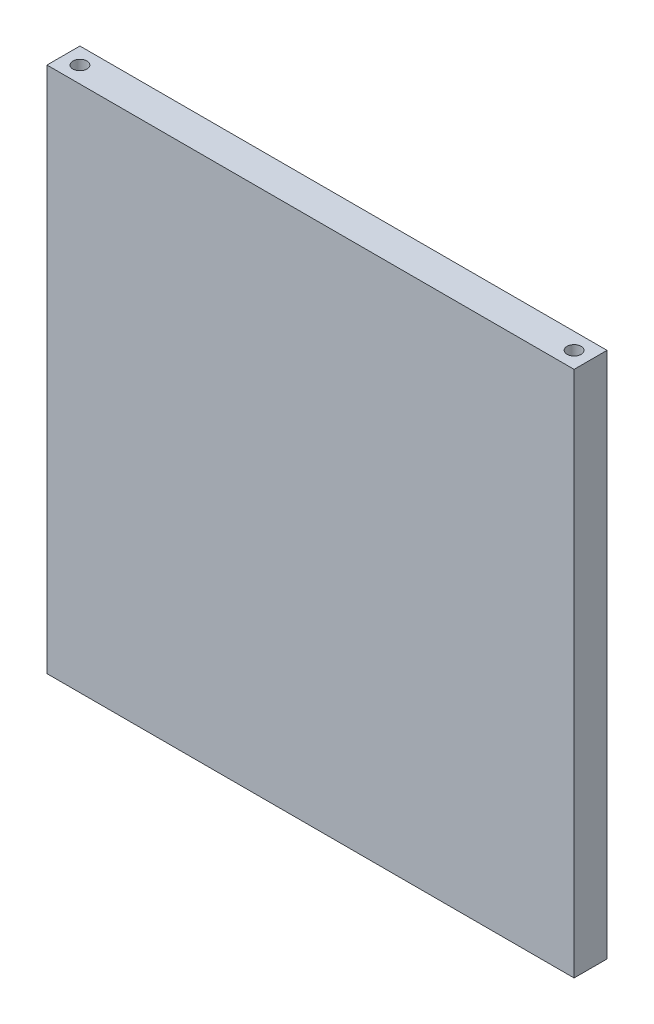
SolidWorks part; units mm, degrees
material "Acrylic (Medium-high impact)"
ref_plane "Front Plane" through (0, 0, 0) normal (0, 0, 1) x (1, 0, 0)
ref_plane "Top Plane" through (0, 0, 0) normal (0, 1, 0) x (1, 0, 0)
ref_plane "Right Plane" through (0, 0, 0) normal (1, 0, 0) x (0, 0, -1)
sketch "Sketch2" plane through (0, 0, 0) normal (0, 0, 1) x (1, 0, 0)
  line L1 (0, 0) -> (101.6, 0)
  line L2 (0, 0) -> (0, 101.6)
  line L3 (0, 101.6) -> (101.6, 101.6)
  line L4 (101.6, 0) -> (101.6, 101.6)
  dimension "D1" = 101.6
  dimension "D2" = 101.6
extrude "Boss-Extrude1" add sketch "Sketch2" along normal blind 6.35
sketch "Sketch4" plane through (0, 101.6, 0) normal (0, 1, 0) x (1, 0, 0)
  line L0 (0, -3.175) -> (101.6, -3.175) construction
  line L1 (0, -6.35) -> (0, 0) construction
  line L2 (101.6, -6.35) -> (101.6, 0) construction
  point P0 (3.175, -3.175)
  point P1 (98.425, -3.175)
  point P8 (0, 0)
  point P9 (0, 0)
  point P10 (0, 0)
  point P11 (0, 0)
  dimension "D1" = 3.175
  dimension "D2" = 3.175
hole_wizard "#6-32 Tapped Hole1" positions "Sketch5" profile "Sketch7" tap size "#6-32" standard "ANSI Inch"
sketch "Sketch5" plane through (0, 101.6, 0) normal (0, 1, 0) x (1, 0, 0)
  point P0 (3.175, -3.175)
  point P3 (98.425, -3.175)
sketch "Sketch7" plane through (3.175, 101.6, 3.175) normal (1, 0, 0) x (0, 0, 1)
  line L0 (0, 0) -> (0, 10.2107)
  line L1 (0, 10.2107) -> (1.3525, 9.398)
  line L2 (1.3525, 9.398) -> (1.3525, 0)
  line L5 (1.3525, 0) -> (0, 0)
  line L10 (0, 10.2107) -> (-1.3525, 9.398) construction
  line L11 (0, -6.35) -> (0, 107.95) construction
  dimension "Tap Drill Dia." = 2.7051
  dimension "Tap Drill Depth" = 9.398
  dimension "Drill Angle" = 118
cosmetic thread "Hole Thread1" parameters "D1"=7.112, "D2"=3.5052
cosmetic thread "Hole Thread2" parameters "D1"=7.112, "D2"=3.5052
ref_point "Point1"
ref_point "Point2"
ref_axis "Axis1" through (101.6, 50.8, 3.175) along (-1, 0, 0)
ref_plane "Plane1" through (0, 50.8, 0) normal (0, 1, 0) x (-1, 0, 0)
mirror "Mirror1" about plane through (0, 50.8, 0) normal (0, 1, 0) of "#6-32 Tapped Hole1"
